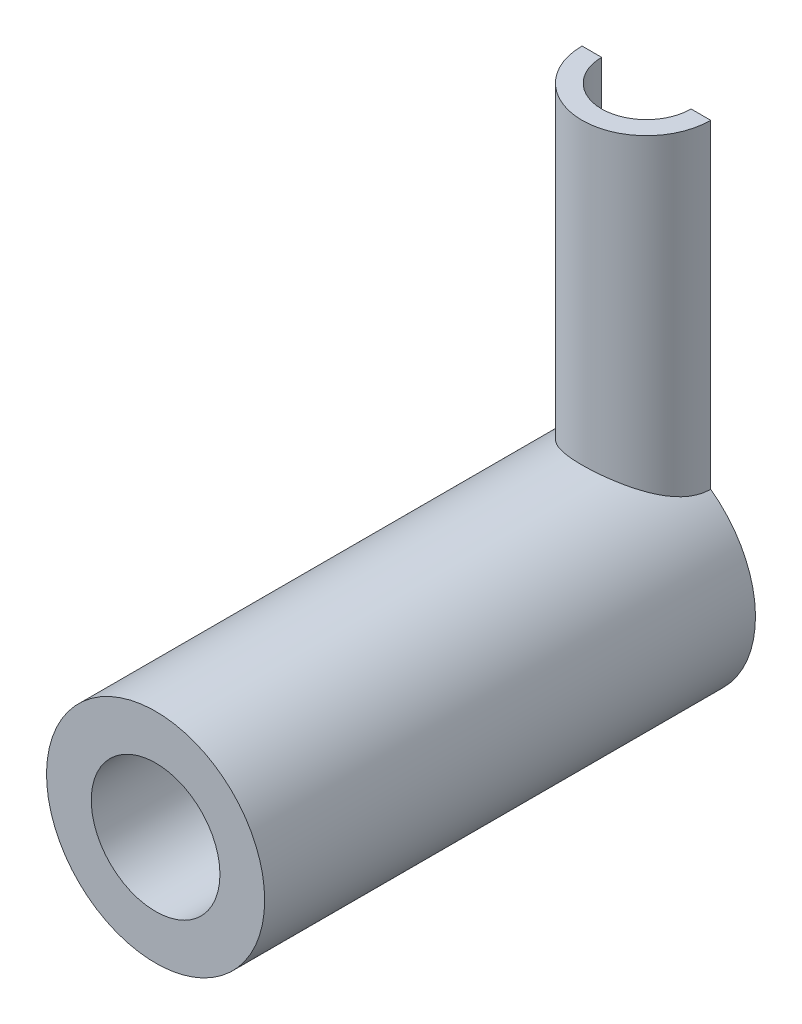
SolidWorks part; units mm, degrees
ref_plane "Front Plane" through (0, 0, 0) normal (0, 0, 1) x (1, 0, 0)
ref_plane "Top Plane" through (0, 0, 0) normal (0, 1, 0) x (1, 0, 0)
ref_plane "Right Plane" through (0, 0, 0) normal (1, 0, 0) x (0, 0, -1)
sketch "Sketch1" plane through (0, 0, 0) normal (0, 0, 1) x (1, 0, 0)
  circle A0 centre (102.3412, 36.4161) radius 5
  circle A1 centre (102.3412, 36.4161) radius 2.95
extrude "Boss-Extrude1" add sketch "Sketch1" along normal blind 2.5
sketch "Sketch2" plane through (0, 0, 2.5) normal (0, 0, 1) x (1, 0, 0)
  circle A0 centre (102.3412, 36.4161) radius 2.95
  circle A1 centre (102.3412, 36.4161) radius 5
extrude "Boss-Extrude2" add sketch "Sketch2" along normal blind 20
sketch "Sketch7" plane through (0, 0, 0) normal (0, 0, -1) x (-1, 0, 0)
  line L1 (-105.2912, 36.4161) -> (-102.3412, 36.4161)
  line L2 (-105.2912, 36.4161) -> (-105.2912, 55.1033)
  line L3 (-105.2912, 55.1033) -> (-102.3412, 55.1033)
  line L4 (-102.3412, 36.4161) -> (-102.3412, 55.1033)
  circle A0 centre (-102.3412, 36.4161) radius 2.95 construction
revolve "Revolve7" add sketch "Sketch7" angle 180 about L4 reverse direction yes
sketch "Sketch8" plane through (0, 0, 0) normal (0, 0, -1) x (-1, 0, 0)
  line L0 (-105.2912, 36.4161) -> (-99.3912, 36.4161) construction
  line L1 (-102.3412, 36.4161) -> (-104.3912, 36.4161)
  line L2 (-102.3412, 36.4161) -> (-102.3412, 56.4161)
  line L3 (-102.3412, 56.4161) -> (-104.3912, 56.4161)
  line L4 (-104.3912, 36.4161) -> (-104.3912, 56.4161)
  dimension "D1" = 20
revolve "Cut-Revolve2" cut sketch "Sketch8" angle 360 about L2
sketch "Sketch9" plane through (0, 0, 0) normal (0, 0, -1) x (-1, 0, 0)
  circle A0 centre (-102.3412, 36.4161) radius 2.95
extrude "Cut-Extrude1" cut sketch "Sketch9" against normal blind 5
